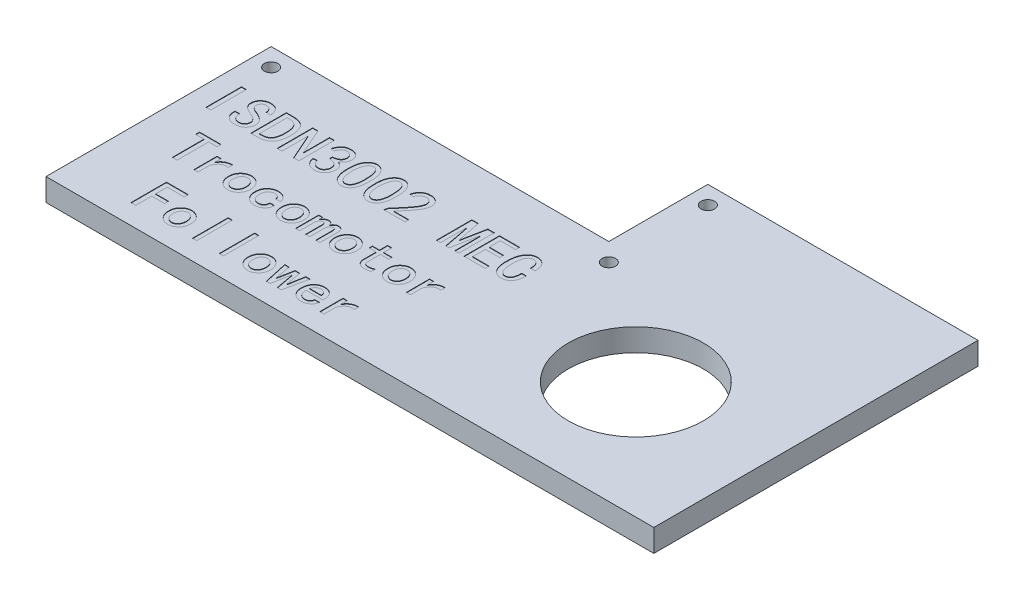
SolidWorks part; units mm, degrees
ref_plane "前视基准面" through (0, 0, 0) normal (0, 0, 1) x (1, 0, 0)
ref_plane "上视基准面" through (0, 0, 0) normal (0, 1, 0) x (1, 0, 0)
ref_plane "右视基准面" through (0, 0, 0) normal (1, 0, 0) x (0, 0, -1)
sketch "Sketch1" plane through (0, 0, 0) normal (0, 1, 0) x (1, 0, 0)
  line L0 (-41.5, -7) -> (33.5, -7)
  line L1 (-37.5, 11) -> (37.5, 11) construction
  line L2 (-37.5, 11) -> (-37.5, -11) construction
  line L3 (-37.5, -11) -> (37.5, -11) construction
  line L4 (37.5, 11) -> (37.5, -11) construction
  line L5 (-37.5, 11) -> (37.5, -11) construction
  line L6 (-37.5, -11) -> (37.5, 11) construction
  line L7 (33.5, -7) -> (33.5, 15)
  line L8 (33.5, 15) -> (93.5, 15)
  line L9 (93.5, 15) -> (93.5, -57)
  line L10 (93.5, -57) -> (-41.5, -57)
  line L11 (-41.5, -57) -> (-41.5, -7)
  line L12 (63.5, 15) -> (63.5, -57) construction
  circle A0 centre (-37.5, -11) radius 1.5
  circle A1 centre (37.5, -11) radius 1.5
  circle A2 centre (37.5, 11) radius 1.5
  circle A3 centre (63.5, -31) radius 15
  point P0 (0, 0)
  dimension "D3" = 3
  dimension "D4" = 3
  dimension "D5" = 3
  dimension "D10" = 20
  dimension "D11" = 30
  dimension "D1" = 22
  dimension "D2" = 75
  dimension "D6" = 4
  dimension "D7" = 4
  dimension "D8" = 4
  dimension "D9" = 4
  dimension "D12" = 30
  dimension "D13" = 30
  dimension "D14" = 50
extrude "Boss-Extrude1" add sketch "Sketch1" along normal blind 5
sketch "Sketch2" plane through (0, 5, 0) normal (0, 1, 0) x (1, 0, 0)
  line L0 (-41.5, -26.1386) -> (33.5, -26.1386) construction
  line L1 (-41.5, -39.5089) -> (33.5, -39.5089) construction
  line L2 (-41.5, -7) -> (-41.5, -57) construction
  line L3 (33.5, -7) -> (33.5, -57) construction
  line L4 (-41.5, -57) -> (93.5, -57) construction
  text T0 "ISDN3002 MEC" font "黑体" height in points 26
  text T1 "Trocomotor\r\nFollower" font "黑体" height in points 26
extrude "Cut-Extrude1" cut sketch "Sketch2" against normal blind 0.1
